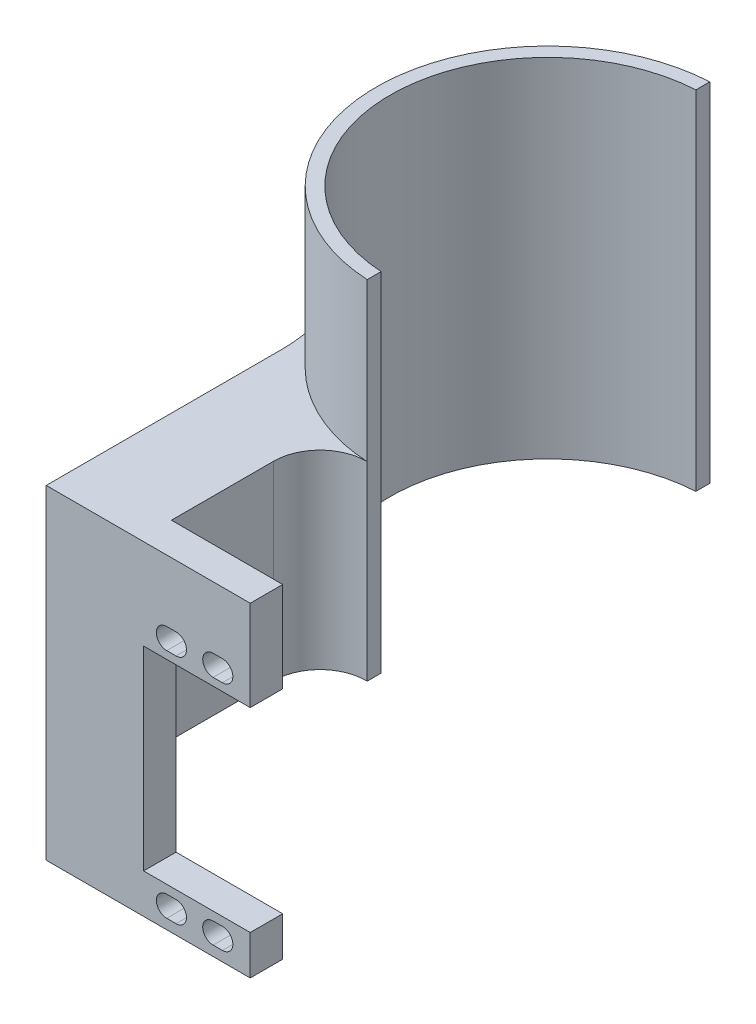
SolidWorks part; units mm, degrees
ref_plane "Plan de face" through (0, 0, 0) normal (0, 0, 1) x (1, 0, 0)
ref_plane "Plan de dessus" through (0, 0, 0) normal (0, 1, 0) x (1, 0, 0)
ref_plane "Plan de droite" through (0, 0, 0) normal (1, 0, 0) x (0, 0, -1)
sketch "Esquisse1" plane through (0, 11.1, 0) normal (0, -1, 0) x (0, 0, 1)
  line L0 (-16.4191, -0.1736) -> (-14.8654, -0.1736) construction
  line L2 (-50.3602, 1.8264) -> (-53.3602, 1.8264)
  line L3 (17.5221, 1.8264) -> (20.5221, 1.8264)
  line L4 (0, 0) -> (85.5357, 0) construction
  circle A0 centre (-16.4191, -0.1736) radius 17.5 construction
  circle A1 centre (0, 0) radius 32 construction
  arc A2 (17.5221, 1.8264) -> (-50.3602, 1.8264) centre (-16.4191, -0.1736) ccw
  arc A3 (20.5221, 1.8264) -> (-53.3602, 1.8264) centre (-16.4191, -0.1736) ccw
  dimension "D1" = 34
  dimension "D4" = 14.4779
  dimension "D2" = 4
  dimension "D3" = 3
extrude "Boss.-Extru.1" add sketch "Esquisse1" along normal blind 75
ref_plane "Plan1" through (0, -92.9, 0) normal (0, -1, 0) x (-1, 0, 0)
sketch "Esquisse3" plane through (0, -92.9, 0) normal (0, -1, 0) x (-1, 0, 0)
  line L0 (32, -1.8432) -> (32, -59.5762)
  line L1 (32, -59.5762) -> (-12, -59.5762)
  line L2 (-12, -59.5762) -> (-12, -52.5762)
  line L3 (-12, -52.5762) -> (12, -52.5762)
  line L5 (12, -52.5762) -> (12, -18.5159)
  line L7 (-10, -52.5762) -> (10, -52.5762) construction
  line L8 (10, -42.2762) -> (10, -50.5762) construction
  line L9 (-10, -52.5762) -> (-10, -50.5762) construction
  arc A0 (1.8264, -20.5221) -> (1.8264, 53.3602) centre (-0.1736, 16.4191) ccw construction
  arc A1 (12, -18.5159) -> (32, -1.8432) centre (-0.1736, 16.4191) ccw
  point P15 (-10, -51.5762)
  dimension "D1" = 2
  dimension "D2" = 2
  dimension "D3" = 7
  dimension "D4" = 20
extrude "Boss.-Extru.2" add sketch "Esquisse3" against normal blind 70
sketch "Esquisse4" plane through (0, -92.9, 0) normal (0, -1, 0) x (1, 0, 0)
  line L0 (-12, 18.5159) -> (-12, 52.5762)
  line L1 (-12, 52.5762) -> (-32, 52.5762)
  line L2 (-32, 59.5762) -> (-32, 1.8432) construction
  line L3 (-32, 52.5762) -> (-32, 1.8432)
  arc A0 (-12, 18.5159) -> (-32, 1.8432) centre (0.1736, -16.4191) ccw construction
  arc A1 (-12, 18.5159) -> (-32, 1.8432) centre (0.1736, -16.4191) ccw
extrude "Enlèv. mat.-Extru.1" cut sketch "Esquisse4" against normal up to surface (29 mm away) up to face at (-16.7112, -63.9, -8.5909)
fillet "Congé1" radius 30 1 edges at (-32, -43.4, 1.8432)
fillet "Congé2" radius 10 1 edges at (-12, -43.4, 18.5159)
sketch "Esquisse5" plane through (0, 0, 52.5762) normal (0, 0, -1) x (-1, 0, 0)
  line L0 (-12, -22.9) -> (-12, -92.9) construction
  line L1 (-12, -42.4) -> (11, -42.4)
  line L2 (-12, -42.4) -> (-12, -84.4)
  line L3 (-12, -84.4) -> (11, -84.4)
  line L4 (11, -42.4) -> (11, -84.4)
  line L5 (10, -83.9) -> (10, -43.1) construction
  line L6 (-10, -83.9) -> (10, -83.9) construction
  line L7 (-6, -38.5) -> (-4, -38.5) construction
  line L8 (-6, -36.25) -> (-4, -36.25)
  line L9 (-6, -40.75) -> (-4, -40.75)
  line L10 (4, -38.5) -> (6, -38.5) construction
  line L11 (4, -36.25) -> (6, -36.25)
  line L12 (4, -40.75) -> (6, -40.75)
  line L13 (-6, -88.5) -> (-4, -88.5) construction
  line L14 (-6, -86.25) -> (-4, -86.25)
  line L15 (-6, -90.75) -> (-4, -90.75)
  line L16 (4, -88.5) -> (6, -88.5) construction
  line L17 (4, -86.25) -> (6, -86.25)
  line L18 (4, -90.75) -> (6, -90.75)
  arc A0 (-6, -36.25) -> (-6, -40.75) centre (-6, -38.5) ccw
  arc A1 (-4, -40.75) -> (-4, -36.25) centre (-4, -38.5) ccw
  arc A2 (4, -36.25) -> (4, -40.75) centre (4, -38.5) ccw
  arc A3 (6, -40.75) -> (6, -36.25) centre (6, -38.5) ccw
  arc A4 (-6, -86.25) -> (-6, -90.75) centre (-6, -88.5) ccw
  arc A5 (-4, -90.75) -> (-4, -86.25) centre (-4, -88.5) ccw
  arc A6 (4, -86.25) -> (4, -90.75) centre (4, -88.5) ccw
  arc A7 (6, -90.75) -> (6, -86.25) centre (6, -88.5) ccw
  point P12 (-5, -38.5)
  point P20 (5, -38.5)
  point P28 (-5, -88.5)
  point P36 (5, -88.5)
  dimension "D1" = 42
  dimension "D2" = 1
  dimension "D3" = 0.5
  dimension "D4" = 4.5
  dimension "D5" = 2
extrude "Enlèv. mat.-Extru.2" cut sketch "Esquisse5" against normal through all
